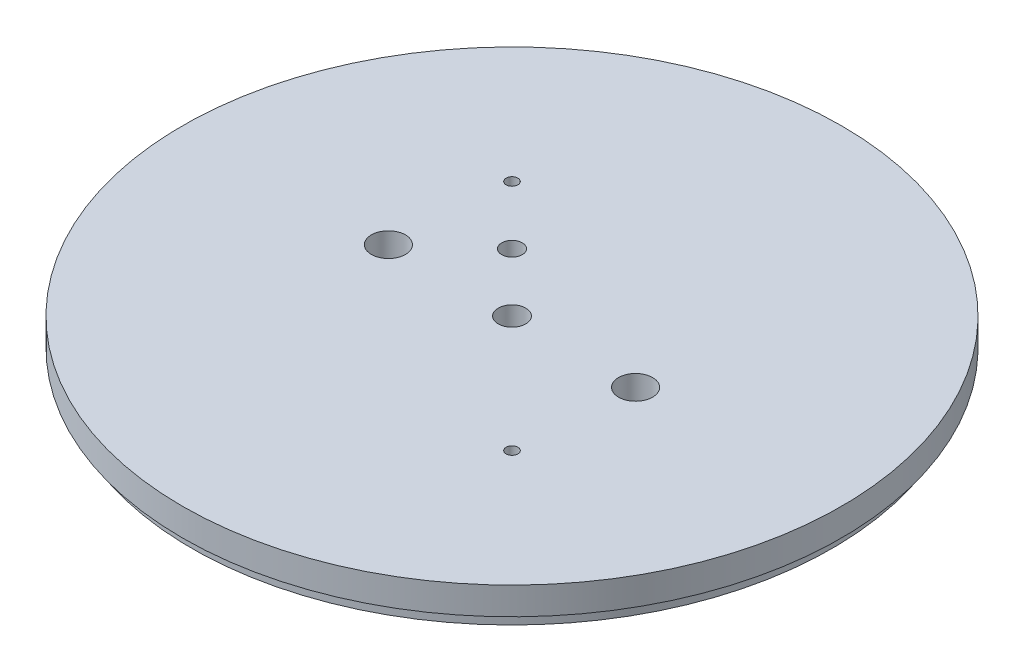
SolidWorks part; units mm, degrees
ref_plane "Front Plane" through (0, 0, 0) normal (0, 0, 1) x (1, 0, 0)
ref_plane "Top Plane" through (0, 0, 0) normal (0, 1, 0) x (1, 0, 0)
ref_plane "Right Plane" through (0, 0, 0) normal (1, 0, 0) x (0, 0, -1)
sketch "Sketch1" plane through (0, 0, 0) normal (0, 1, 0) x (1, 0, 0)
  line L0 (0, -76.2) -> (0, 76.2) construction
  line L1 (-76.2, 0) -> (76.2, 0) construction
  line L2 (-26.9408, 26.9408) -> (0, 0) construction
  line L3 (0, 56.7387) -> (0, 29.6936) construction
  line L4 (3.6407, 56.7387) -> (3.6407, 29.6936) construction
  line L5 (-3.6407, 56.7387) -> (-3.6407, 29.6936) construction
  line L6 (0, -56.7387) -> (0, -29.6936) construction
  line L7 (3.6407, -56.7387) -> (3.6407, -29.6936) construction
  line L8 (-3.6407, -56.7387) -> (-3.6407, -29.6936) construction
  line L9 (-53.8815, -53.8815) -> (54.3236, 54.3236) construction
  circle A0 centre (0, 0) radius 76.2
  circle A1 centre (0, 0) radius 3.175
  circle A2 centre (28.575, 0) radius 3.937
  circle A3 centre (-28.575, 0) radius 3.937
  circle A4 centre (-26.9408, 26.9408) radius 1.3589
  arc A6 (3.6407, 56.7387) -> (-3.6407, 56.7387) centre (0, 56.7387) ccw construction
  arc A7 (-3.6407, 29.6936) -> (3.6407, 29.6936) centre (0, 29.6936) ccw construction
  arc A8 (3.6407, -56.7387) -> (-3.6407, -56.7387) centre (0, -56.7387) cw construction
  arc A9 (-3.6407, -29.6936) -> (3.6407, -29.6936) centre (0, -29.6936) cw construction
  circle A10 centre (26.9408, -26.9408) radius 1.3589
  circle A11 centre (-13.4704, 13.4704) radius 2.3813
  point P16 (0, 43.2162)
  point P19 (0, 0)
  point P26 (0, -43.2162)
  dimension "D1" = 152.4
  dimension "D2" = 6.35
  dimension "D3" = 7.874
  dimension "D5" = 2.7178
  dimension "D8" = 4.7625
  dimension "D6" = 38.1
  dimension "D7" = 45
  dimension "D4" = 45
  dimension "D9" = 28.575
extrude "Boss-Extrude1" add sketch "Sketch1" along normal blind 9.525
sketch "Sketch2" plane through (0, 0, 0) normal (0, -1, 0) x (1, 0, 0)
  circle A0 centre (0, 0) radius 76.2
  circle A1 centre (0, 0) radius 74.041
  dimension "D1" = 152.4
  dimension "D2" = 148.082
extrude "Cut-Extrude1" cut sketch "Sketch2" against normal blind 3.175
sketch "Sketch3" plane through (0, 9.525, 0) normal (0, 1, 0) x (1, 0, 0)
  line L0 (0, 76.2) -> (0, -76.2) construction
  line L1 (-76.2, 0) -> (76.2, 0) construction
  line L2 (0, 34.798) -> (0, 13.97) construction
  line L3 (3.2385, 34.798) -> (3.2385, 13.97)
  line L4 (-3.2385, 34.798) -> (-3.2385, 13.97)
  line L5 (0, -34.798) -> (0, -13.97) construction
  line L6 (3.2385, -34.798) -> (3.2385, -13.97)
  line L7 (-3.2385, -34.798) -> (-3.2385, -13.97)
  circle A0 centre (0, 0) radius 76.2 construction
  arc A1 (3.2385, 34.798) -> (-3.2385, 34.798) centre (0, 34.798) ccw
  arc A2 (-3.2385, 13.97) -> (3.2385, 13.97) centre (0, 13.97) ccw
  arc A3 (3.2385, -34.798) -> (-3.2385, -34.798) centre (0, -34.798) cw
  arc A4 (-3.2385, -13.97) -> (3.2385, -13.97) centre (0, -13.97) cw
  point P7 (0, 13.97)
  point P8 (0, 34.798)
  point P12 (0, 24.384)
  point P20 (0, -24.384)
  point P25 (0, -34.798)
  point P26 (0, -13.97)
  dimension "D1" = 13.97
  dimension "D2" = 20.828
  dimension "D3" = 6.477
extrude "Cut-Extrude2" cut sketch "Sketch3" against normal blind 3.556 from offset 5.969 offset against normal yes
equation "\"leadDist\"=1.5"
equation "\"Lead_Screw_Dist\" = 2.25in"
equation "\"D9@Sketch1\"=\"Lead_Screw_Dist\"/2"
